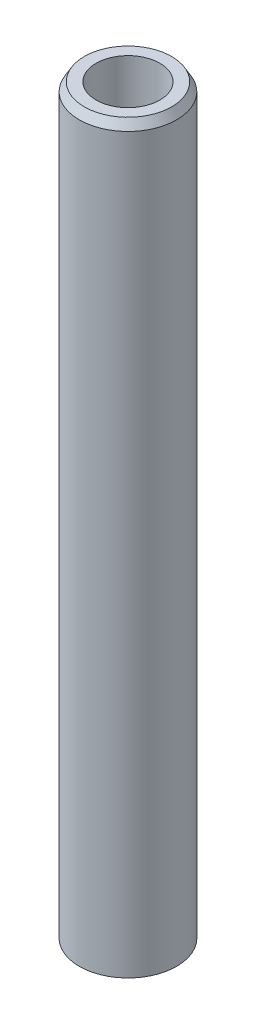
SolidWorks part; units mm, degrees
ref_plane "Front Plane" through (0, 0, 0) normal (0, 0, 1) x (1, 0, 0)
ref_plane "Top Plane" through (0, 0, 0) normal (0, 1, 0) x (1, 0, 0)
ref_plane "Right Plane" through (0, 0, 0) normal (1, 0, 0) x (0, 0, -1)
sketch "Sketch1" plane through (0, 0, 0) normal (0, 1, 0) x (1, 0, 0)
  circle A0 centre (0, 0) radius 20
  dimension "SHAFT_OD" = 40
extrude "Boss-Extrude1" add sketch "Sketch1" along normal blind 306.705
sketch "Sketch2" plane through (0, 0, 0) normal (0, 1, 0) x (1, 0, 0)
  circle A0 centre (0, 0) radius 13.104
  dimension "BORE_D" = 26.2081
extrude "Cut-Extrude1" cut sketch "Sketch2" along normal through all
chamfer "Chamfer1" distance 3.5861 angle 30 2 edges at (0, 306.705, 20) (0, 0, 20) first distance on face at (0, 306.705, 20) first distance on face at (0, 0, 13.104)
